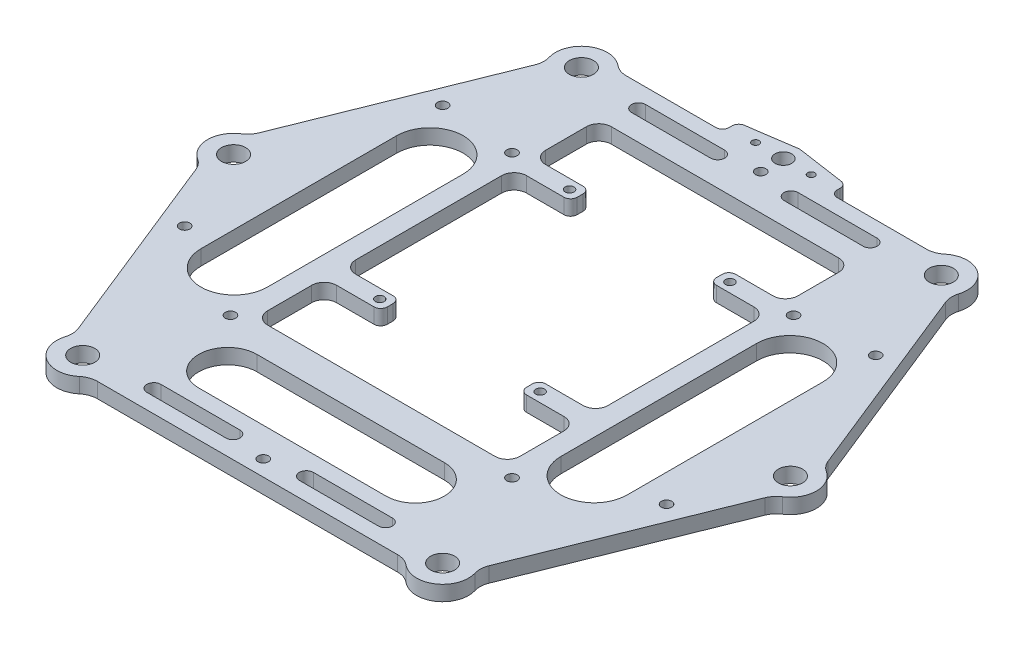
SolidWorks part; units mm, degrees
material "Custom Plastic"
ref_plane "Front Plane" through (0, 0, 0) normal (0, 0, 1) x (1, 0, 0)
ref_plane "Top Plane" through (0, 0, 0) normal (0, 1, 0) x (1, 0, 0)
ref_plane "Right Plane" through (0, 0, 0) normal (1, 0, 0) x (0, 0, -1)
sketch "Sketch1" plane through (0, 0, 0) normal (0, 1, 0) x (1, 0, 0)
  line L0 (0, 0) -> (0, 80.8355) construction
  line L1 (0, 0) -> (0, -80.8355) construction
  line L2 (0, 0) -> (0, 60.6933) construction
  line L3 (0, 0) -> (0, -60.6933) construction
  line L4 (0, 0) -> (85.09, 0) construction
  line L5 (0, 0) -> (-85.09, 0) construction
  line L6 (0, 0) -> (-54.991, 76.2) construction
  line L7 (0, 0) -> (54.991, -76.2) construction
  line L8 (0, 0) -> (54.991, 76.2) construction
  line L9 (0, 0) -> (-54.991, -76.2) construction
  line L10 (-54.991, 0) -> (-54.991, 76.2) construction
  line L11 (-54.991, 0) -> (-54.991, -76.2) construction
  line L12 (0, 80.8355) -> (58.3363, 80.8355)
  line L13 (0, 80.8355) -> (-58.3363, 80.8355)
  line L14 (58.3363, 80.8355) -> (54.991, 76.2) construction
  line L15 (85.09, 0) -> (90.8065, 0) construction
  line L16 (58.3363, 80.8355) -> (90.8065, 0)
  line L17 (0, 60.6933) -> (43.8003, 60.6933)
  line L19 (54.991, -76.2) -> (58.3363, -80.8355) construction
  line L20 (-54.991, -76.2) -> (-58.3363, -80.8355) construction
  line L21 (-85.09, 0) -> (-90.8065, 0) construction
  line L22 (90.8065, 0) -> (58.3363, -80.8355)
  line L23 (58.3363, -80.8355) -> (-58.3363, -80.8355)
  line L24 (-58.3363, -80.8355) -> (-90.8065, 0)
  line L25 (-90.8065, 0) -> (-58.3363, 80.8355)
  line L26 (0, 60.6933) -> (-43.8003, 60.6933)
  line L29 (-43.947, -60.8965) -> (43.947, -60.8965)
  line L31 (43.8003, 60.6933) -> (68.1798, 0)
  line L32 (68.1798, 0) -> (43.947, -60.8965)
  line L33 (-43.8003, 60.6933) -> (-68.1798, 0)
  line L34 (-68.1798, 0) -> (-43.947, -60.8965)
  circle A0 centre (54.991, 76.2) radius 7.9375
  circle A1 centre (85.09, 0) radius 7.9375
  circle A2 centre (54.991, -76.2) radius 7.9375
  circle A3 centre (-54.991, -76.2) radius 7.9375
  circle A4 centre (-85.09, 0) radius 7.9375
  circle A5 centre (-54.991, 76.2) radius 7.9375
  dimension "D6" = 15.875
  dimension "D1" = 161.671
  dimension "D2" = 20.1422
  dimension "D3" = 152.4
  dimension "D4" = 109.982
  dimension "D5" = 170.18
  dimension "D7" = 19.939
extrude "Boss-Extrude1" add sketch "Sketch1" along normal blind 4.6228 contours L25 L24 L23 L22 L16 L12 L13 L32 L29 L34 L33 L26 L17 L31 | L13 A5 L25 | L25 A5 L13 | L16 A0 L12 | L12 A0 L16 | L22 A1 L16 | L16 A1 L22 | L23 A2 L22 | L22 A2 L23 | L23 A3 L24 | L24 A3 L23 | L24 A4 L25 | L25 A4 L24 | L33 L34 L29 L32 L31 L17 L26 region at (24.2739, 0, -78.4484) region at (57.3688, 0, -83.5766) region at (54.1136, 0, -74.8115) region at (-54.1136, 0, -74.8115) region at (-53.442, 0, -81.0227) region at (91.4646, 0, -4.4593) region at (83.9088, 0, 0) region at (-83.9088, 0, 0) region at (-89.4556, 0, -3.7871) region at (62.4664, 0, 74.1539) region at (54.1136, 0, 74.8115) region at (-54.1136, 0, 74.8115) region at (-60.2528, 0, 76.5663) region at (0, 0, 0.1208)
hole_wizard "L (0.29) Diameter Hole1" positions "Sketch2" profile "Sketch3" hole size "L" standard "ANSI Inch" end condition through all
sketch "Sketch2" plane through (0, 4.6228, 0) normal (0, 1, 0) x (1, 0, 0)
  point P0 (-54.991, 76.2)
  point P3 (85.09, 0)
  point P5 (54.991, 76.2)
  point P7 (54.991, -76.2)
  point P10 (-54.991, -76.2)
  point P12 (-85.09, 0)
sketch "Sketch3" plane through (-54.991, 4.6228, -76.2) normal (1, 0, 0) x (0, 0, 1)
  line L0 (0, 0) -> (0, 4.6228)
  line L1 (0, 4.6228) -> (3.683, 4.6228)
  line L2 (3.683, 4.6228) -> (3.683, 0)
  line L5 (3.683, 0) -> (0, 0)
  line L11 (0, -6.35) -> (0, 107.95) construction
  dimension "Thru Hole Dia." = 7.366
  dimension "Thru Hole Depth" = 4.6228
sketch "Sketch4" plane through (0, 0, 0) normal (0, 1, 0) x (1, 0, 0)
  line L10 (0, 0) -> (0, 76.0095) construction
  line L11 (0, 0) -> (0, -76.0095) construction
  line L12 (0, 76.0095) -> (0, 80.8355) construction
  line L13 (0, -76.0095) -> (0, -80.8355) construction
  line L14 (-48.5477, 80.8355) -> (48.5477, 80.8355) construction
  line L15 (48.5477, -80.8355) -> (-48.5477, -80.8355) construction
  line L16 (0, 44.9702) -> (66.1733, 44.9702) construction
  line L17 (0, 44.9702) -> (-66.1733, 44.9702) construction
  line L18 (0, -26.3953) -> (73.6346, -26.3953) construction
  line L19 (0, -26.3953) -> (-73.6346, -26.3953) construction
  line L20 (-66.1733, 44.9702) -> (-71.8301, 47.2424) construction
  line L21 (-87.8114, 7.4564) -> (-61.822, 72.1576) construction
  line L22 (-73.6346, -26.3953) -> (-79.2913, -28.6675) construction
  line L23 (-61.822, -72.1576) -> (-87.8114, -7.4564) construction
  circle A0 centre (0, 76.0095) radius 1.5875
  circle A1 centre (-66.1733, 44.9702) radius 1.5875
  circle A2 centre (-73.6346, -26.3953) radius 1.5875
  circle A3 centre (66.1733, 44.9702) radius 1.5875
  circle A4 centre (73.6346, -26.3953) radius 1.5875
  circle A5 centre (0, -76.0095) radius 1.5875
  dimension "D3" = 3.175
  dimension "D1" = 71.3655
  dimension "D2" = 44.9702
  dimension "D4" = 152.019
  dimension "D5" = 132.3467
  dimension "D6" = 6.096
  dimension "D7" = 147.2692
extrude "Cut-Extrude1" cut sketch "Sketch4" along normal through all contours A2 | A1 | A0 | A3 | A4 | A5 region at (-73.6346, 0, 26.3953)
fillet "Fillet1" radius 6.35 12 edges at (-48.5477, 2.3114, -80.8355) (48.5477, 2.3114, -80.8355) (61.822, 2.3114, -72.1576) (87.8114, 2.3114, -7.4564) (87.8114, 2.3114, 7.4564) (61.822, 2.3114, 72.1576) (-48.5477, 2.3114, 80.8355) (48.5477, 2.3114, 80.8355) (-61.822, 2.3114, 72.1576) (-87.8114, 2.3114, 7.4564) (-87.8114, 2.3114, -7.4564) (-61.822, 2.3114, -72.1576)
sketch "Sketch9" plane through (0, 4.6228, 0) normal (0, 1, 0) x (1, 0, 0)
  line L0 (54.991, 76.2) -> (54.991, -76.2) construction
  line L1 (-54.991, 76.2) -> (-54.991, -76.2) construction
  line L2 (-85.09, 0) -> (85.09, 0) construction
  line L3 (-54.991, 0) -> (-54.991, 40.0685) construction
  line L4 (54.991, 0) -> (54.991, 40.0685) construction
  line L5 (-54.991, 29.9085) -> (-54.991, -29.9085) construction
  line L6 (-44.831, 29.9085) -> (-44.831, -29.9085)
  line L7 (-65.151, 29.9085) -> (-65.151, -29.9085)
  line L8 (54.991, -29.9085) -> (54.991, 29.9085) construction
  line L9 (44.831, -29.9085) -> (44.831, 29.9085)
  line L10 (65.151, -29.9085) -> (65.151, 29.9085)
  line L11 (-54.991, 0) -> (-54.991, -40.0685) construction
  line L12 (54.991, 0) -> (54.991, -40.0685) construction
  line L13 (44.831, 29.9085) -> (65.151, 29.9085) construction
  line L14 (-65.151, 29.9085) -> (-44.831, 29.9085) construction
  arc A0 (-44.831, 29.9085) -> (-65.151, 29.9085) centre (-54.991, 29.9085) ccw
  arc A1 (-65.151, -29.9085) -> (-44.831, -29.9085) centre (-54.991, -29.9085) ccw
  arc A2 (44.831, -29.9085) -> (65.151, -29.9085) centre (54.991, -29.9085) ccw
  arc A3 (65.151, 29.9085) -> (44.831, 29.9085) centre (54.991, 29.9085) ccw
  point P18 (-54.991, 0)
  point P24 (54.991, 0)
  dimension "D1" = 20.32
  dimension "D2" = 80.137
extrude "Cut-Extrude2" cut sketch "Sketch9" against normal through all contours L10 A3 L9 A2 | A0 L7 A1 L6 region at (54.991, 4.6228, 0)
sketch "Sketch11" plane through (0, 4.6228, 0) normal (0, 1, 0) x (1, 0, 0)
  line L0 (-54.991, 76.2) -> (54.991, 76.2) construction
  line L1 (0, 76.2) -> (0, 74.0664) construction
  line L2 (0, 74.0664) -> (23.3045, 74.0664) construction
  line L3 (0, 74.0664) -> (-23.3045, 74.0664) construction
  line L4 (35.3949, 74.0664) -> (11.2141, 74.0664) construction
  line L5 (35.3949, 71.9328) -> (11.2141, 71.9328)
  line L6 (35.3949, 76.2) -> (11.2141, 76.2)
  line L7 (-35.3949, 74.0664) -> (-11.2141, 74.0664) construction
  line L8 (-35.3949, 76.2) -> (-11.2141, 76.2)
  line L9 (-35.3949, 71.9328) -> (-11.2141, 71.9328)
  line L10 (23.3045, 74.0664) -> (37.5285, 74.0664) construction
  line L11 (23.3045, 74.0664) -> (9.0805, 74.0664) construction
  line L12 (-23.3045, 74.0664) -> (-9.0805, 74.0664) construction
  line L13 (-85.09, 0) -> (85.09, 0) construction
  line L14 (-23.3045, -74.0664) -> (-9.0805, -74.0664) construction
  line L15 (23.3045, -74.0664) -> (9.0805, -74.0664) construction
  line L16 (23.3045, -74.0664) -> (37.5285, -74.0664) construction
  line L17 (0, -74.0664) -> (-23.3045, -74.0664) construction
  line L18 (0, -74.0664) -> (23.3045, -74.0664) construction
  line L19 (0, -76.2) -> (0, -74.0664) construction
  line L20 (-35.3949, -74.0664) -> (-11.2141, -74.0664) construction
  line L21 (-35.3949, -76.2) -> (-11.2141, -76.2)
  line L22 (-35.3949, -71.9328) -> (-11.2141, -71.9328)
  line L23 (35.3949, -74.0664) -> (11.2141, -74.0664) construction
  line L24 (35.3949, -71.9328) -> (11.2141, -71.9328)
  line L25 (35.3949, -76.2) -> (11.2141, -76.2)
  line L26 (0, -74.0664) -> (0, -58.2168) construction
  line L27 (-28.6385, -58.2168) -> (28.6385, -58.2168) construction
  line L28 (-28.6385, -49.3268) -> (28.6385, -49.3268)
  line L29 (-28.6385, -67.1068) -> (28.6385, -67.1068)
  line L30 (37.5285, -74.0664) -> (37.5285, -58.2168) construction
  line L31 (0, -58.2168) -> (0, 12.573) construction
  line L32 (45.8558, -80.8355) -> (-45.8558, -80.8355) construction
  line L33 (-38.5445, -39.9415) -> (38.5445, -39.9415)
  line L34 (-38.5445, -39.9415) -> (-38.5445, 65.0875)
  line L35 (-38.5445, 65.0875) -> (38.5445, 65.0875)
  line L36 (38.5445, -39.9415) -> (38.5445, 65.0875)
  line L37 (-38.5445, -39.9415) -> (38.5445, 65.0875) construction
  line L38 (-38.5445, 65.0875) -> (38.5445, -39.9415) construction
  arc A0 (35.3949, 71.9328) -> (35.3949, 76.2) centre (35.3949, 74.0664) ccw
  arc A1 (11.2141, 76.2) -> (11.2141, 71.9328) centre (11.2141, 74.0664) ccw
  arc A2 (-35.3949, 76.2) -> (-35.3949, 71.9328) centre (-35.3949, 74.0664) ccw
  arc A3 (-11.2141, 71.9328) -> (-11.2141, 76.2) centre (-11.2141, 74.0664) ccw
  arc A4 (-35.3949, -76.2) -> (-35.3949, -71.9328) centre (-35.3949, -74.0664) cw
  arc A5 (-11.2141, -71.9328) -> (-11.2141, -76.2) centre (-11.2141, -74.0664) cw
  arc A6 (35.3949, -71.9328) -> (35.3949, -76.2) centre (35.3949, -74.0664) cw
  arc A7 (11.2141, -76.2) -> (11.2141, -71.9328) centre (11.2141, -74.0664) cw
  arc A8 (-28.6385, -49.3268) -> (-28.6385, -67.1068) centre (-28.6385, -58.2168) ccw
  arc A9 (28.6385, -67.1068) -> (28.6385, -49.3268) centre (28.6385, -58.2168) ccw
  point P10 (23.3045, 74.0664)
  point P17 (-23.3045, 74.0664)
  point P39 (-23.3045, -74.0664)
  point P46 (23.3045, -74.0664)
  point P54 (0, -58.2168)
  dimension "D1" = 4.2672
  dimension "D2" = 28.448
  dimension "D3" = 18.161
  dimension "D4" = 4.826
  dimension "D5" = 17.78
  dimension "D6" = 77.089
  dimension "D7" = 105.029
  dimension "D8" = 40.894
extrude "Cut-Extrude3" cut sketch "Sketch11" against normal through all
sketch "Sketch12" plane through (0, 4.6228, 0) normal (0, 1, 0) x (1, 0, 0)
  line L0 (-38.5445, 65.0875) -> (-38.5445, -39.9415) construction
  line L1 (-38.5445, 45.0215) -> (-21.2725, 45.0215)
  line L2 (-38.5445, 45.0215) -> (-38.5445, 39.1795)
  line L3 (-38.5445, 39.1795) -> (-21.2725, 39.1795)
  line L4 (-21.2725, 45.0215) -> (-21.2725, 39.1795)
  line L5 (38.5445, -39.9415) -> (38.5445, 65.0875) construction
  line L6 (38.5445, 45.0215) -> (21.2725, 45.0215)
  line L7 (38.5445, 45.0215) -> (38.5445, 39.1795)
  line L8 (38.5445, 39.1795) -> (21.2725, 39.1795)
  line L9 (21.2725, 45.0215) -> (21.2725, 39.1795)
  line L10 (38.5445, 65.0875) -> (-38.5445, 65.0875) construction
  line L11 (-38.5445, -13.0175) -> (-21.2725, -13.0175)
  line L12 (-38.5445, -13.0175) -> (-38.5445, -18.8595)
  line L13 (-38.5445, -18.8595) -> (-21.2725, -18.8595)
  line L14 (-21.2725, -13.0175) -> (-21.2725, -18.8595)
  line L15 (38.5445, -13.0175) -> (21.2725, -13.0175)
  line L16 (38.5445, -13.0175) -> (38.5445, -18.8595)
  line L17 (38.5445, -18.8595) -> (21.2725, -18.8595)
  line L18 (21.2725, -13.0175) -> (21.2725, -18.8595)
  line L19 (-38.5445, -39.9415) -> (38.5445, -39.9415) construction
  dimension "D1" = 5.842
  dimension "D2" = 17.272
  dimension "D3" = 20.066
  dimension "D4" = 21.082
extrude "Boss-Extrude2" add sketch "Sketch12" against normal up to surface (4.6228 mm away) up to face at (0, 0, 58.2168)
fillet "Fillet2" radius 3.81 12 edges at (38.5445, 2.3114, 39.9415) (-38.5445, 2.3114, 39.9415) (-38.5445, 2.3114, 18.8595) (38.5445, 2.3114, 18.8595) (-38.5445, 2.3114, 13.0175) (38.5445, 2.3114, 13.0175) (38.5445, 2.3114, -39.1795) (-38.5445, 2.3114, -39.1795) (-38.5445, 2.3114, -45.0215) (38.5445, 2.3114, -45.0215) (38.5445, 2.3114, -65.0875) (-38.5445, 2.3114, -65.0875)
fillet "Fillet3" radius 2.032 8 edges at (-21.2725, 2.3114, 13.0175) (21.2725, 2.3114, 13.0175) (-21.2725, 2.3114, 18.8595) (21.2725, 2.3114, 18.8595) (21.2725, 2.3114, -39.1795) (21.2725, 2.3114, -45.0215) (-21.2725, 2.3114, -39.1795) (-21.2725, 2.3114, -45.0215)
sketch "Sketch13" plane through (0, 4.6228, 0) normal (0, 1, 0) x (1, 0, 0)
  line L0 (0, -39.9415) -> (0, -15.9004) construction
  line L1 (24.4996, 42.1005) -> (-24.4996, 42.1005) construction
  line L2 (24.4996, 42.1005) -> (24.4996, -15.9004) construction
  line L3 (24.4996, -15.9004) -> (-24.4996, -15.9004) construction
  line L4 (-24.4996, 42.1005) -> (-24.4996, -15.9004) construction
  line L5 (-34.7345, -39.9415) -> (34.7345, -39.9415) construction
  line L6 (24.4996, 39.1795) -> (24.4996, 45.0215) construction
  line L8 (23.3045, 39.1795) -> (34.7345, 39.1795) construction
  line L11 (34.7345, 45.0215) -> (23.3045, 45.0215) construction
  circle A0 centre (-24.4996, 42.1005) radius 1.35
  circle A1 centre (24.4996, 42.1005) radius 1.35
  circle A2 centre (24.4996, -15.9004) radius 1.35
  circle A3 centre (-24.4996, -15.9004) radius 1.35
  dimension "D3" = 2.7
  dimension "D1" = 48.9991
  dimension "D2" = 58.0009
extrude "Cut-Extrude4" cut sketch "Sketch13" against normal through all
sketch "Sketch14" plane through (0, 4.6228, 0) normal (0, 1, 0) x (1, 0, 0)
  line L0 (-43.0213, 43.0212) -> (43.0213, -43.0213) construction
  line L1 (43.0212, 43.0212) -> (-43.0213, 43.0212) construction
  line L2 (43.0212, 43.0212) -> (43.0213, -43.0213) construction
  line L3 (43.0213, -43.0213) -> (-43.0213, -43.0213) construction
  line L4 (-43.0213, 43.0212) -> (-43.0213, -43.0213) construction
  line L6 (-54.991, 76.2) -> (54.991, -76.2) construction
  line L7 (54.991, 76.2) -> (-54.991, -76.2) construction
  line L8 (43.0212, 43.0212) -> (-43.0213, -43.0213) construction
  circle A0 centre (43.0212, 43.0212) radius 1.5875
  circle A1 centre (-43.0213, 43.0212) radius 1.5875
  circle A2 centre (43.0213, -43.0213) radius 1.5875
  circle A3 centre (-43.0213, -43.0213) radius 1.5875
  point P4 (0, 0)
  point P5 (0, 0)
  dimension "D2" = 3.175
  dimension "D1" = 86.0425
extrude "Cut-Extrude5" cut sketch "Sketch14" against normal through all
sketch "Sketch15" plane through (0, 4.6228, 0) normal (0, 1, 0) x (1, 0, 0)
  line L0 (0, 80.8355) -> (0, 87.9475) construction
  line L1 (-45.8558, 80.8355) -> (45.8558, 80.8355) construction
  line L2 (0, 87.9475) -> (16.51, 85.5345)
  line L3 (16.51, 85.5345) -> (16.51, 80.8355)
  line L4 (16.51, 80.8355) -> (0, 80.8355)
  line L5 (0, 80.8355) -> (-16.51, 80.8355)
  line L6 (-16.51, 80.8355) -> (-16.51, 85.5345)
  line L8 (-16.51, 85.5345) -> (0, 87.9475)
  line L9 (0, 87.9475) -> (0, 85.471) construction
  line L10 (0, 76.0095) -> (0, 77.597) construction
  line L11 (0, 77.597) -> (0, 80.391) construction
  line L12 (34.7345, 65.0875) -> (-34.7345, 65.0875) construction
  line L13 (0, 82.931) -> (8.5001, 82.931) construction
  line L14 (0, 82.931) -> (-8.5001, 82.931) construction
  circle A1 centre (0, 82.931) radius 2.54
  circle A2 centre (0, 76.0095) radius 1.5875 construction
  circle A3 centre (-8.5001, 82.931) radius 1.0795
  circle A4 centre (8.5001, 82.931) radius 1.0795
  dimension "D1" = 5.08
  dimension "D7" = 2.159
  dimension "D2" = 33.02
  dimension "D3" = 4.699
  dimension "D4" = 22.86
  dimension "D5" = 2.794
  dimension "D6" = 17.0002
extrude "Boss-Extrude3" add sketch "Sketch15" against normal up to surface (4.6228 mm away) contours A1 L4 L3 L2 L8 L6 L5 region at (8.2062, 4.6228, -86.4068) up to face at (-43.0213, 0, -41.4337)
extrude "Cut-Extrude6" cut sketch "Sketch15<3>" against normal through all contours A1
sketch "Sketch15<3>" plane through (0, 4.6228, 0) normal (0, 1, 0) x (1, 0, 0) same geometry as "Sketch15"
fillet "Fillet4" radius 2.032 5 edges at (16.51, 2.3114, -80.8355) (-16.51, 2.3114, -80.8355) (16.51, 2.3114, -85.5345) (0, 2.3114, -87.9475) (-16.51, 2.3114, -85.5345)
